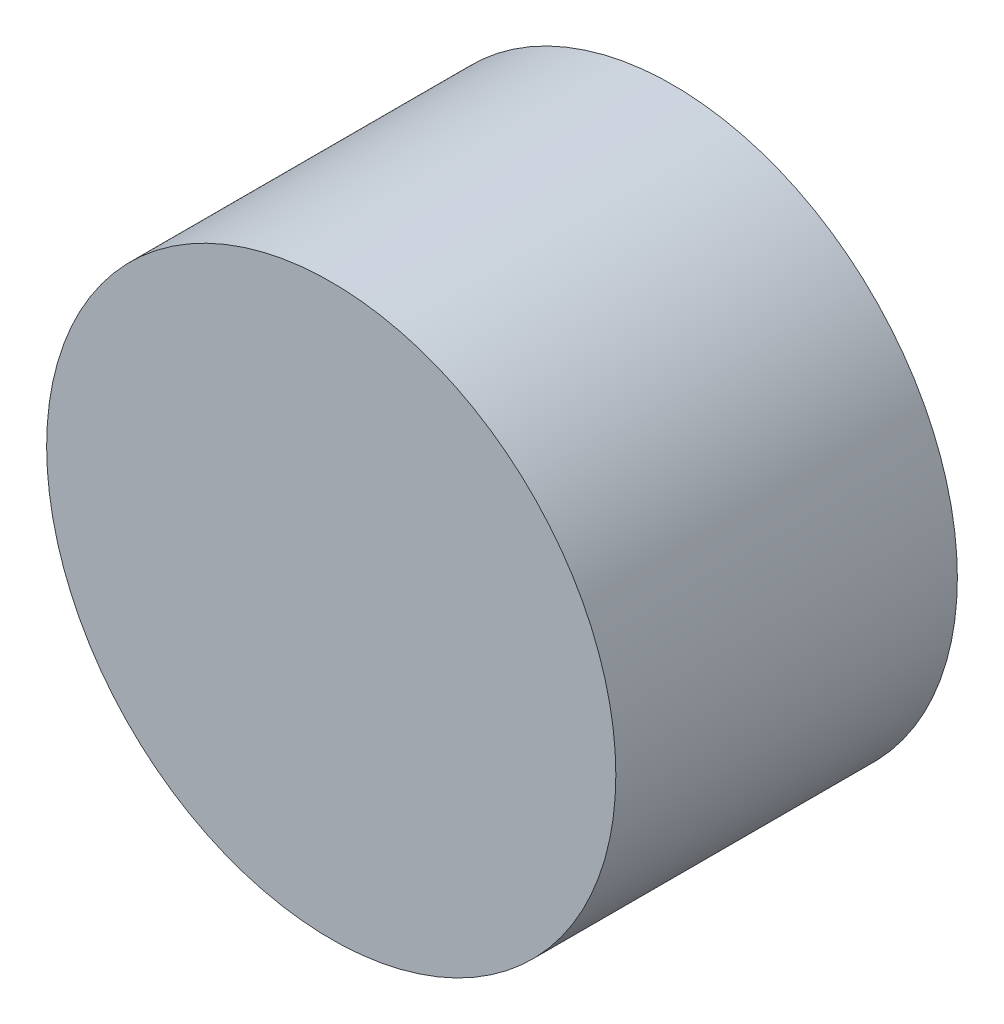
SolidWorks part; units mm, degrees
ref_plane "前视基准面" through (0, 0, 0) normal (0, 0, 1) x (1, 0, 0)
ref_plane "上视基准面" through (0, 0, 0) normal (0, 1, 0) x (1, 0, 0)
ref_plane "右视基准面" through (0, 0, 0) normal (1, 0, 0) x (0, 0, -1)
other "Configuration Table"
sketch "Sketch1" plane through (0, 0, 0) normal (0, 0, 1) x (1, 0, 0)
  circle A0 centre (0, 0) radius 50
extrude "Boss-Extrude1" add sketch "Sketch1" along normal blind 60
ref_plane "mount_face_bottom" through (0, 0, 0) normal (0, 0, 1) x (1, 0, 0)
ref_plane "mount_face_top" through (0, 0, 60) normal (0, 0, 1) x (1, 0, 0)
sketch3d "3DSketch1"
  line L0 (0, 0, 0) -> (0, 0, 60) construction
ref_axis "main_axis_z" through (0, 0, 0) along (0, 0, 1)
